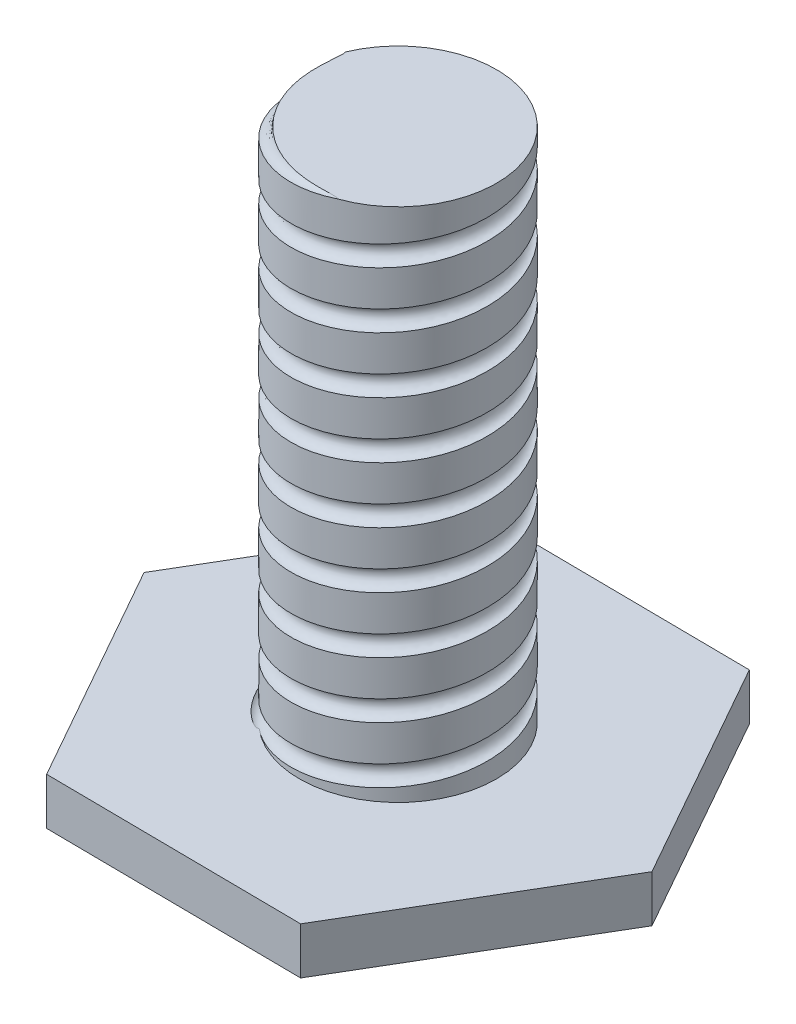
SolidWorks part; units mm, degrees
ref_plane "Front Plane" through (0, 0, 0) normal (0, 0, 1) x (1, 0, 0)
ref_plane "Top Plane" through (0, 0, 0) normal (0, 1, 0) x (1, 0, 0)
ref_plane "Right Plane" through (0, 0, 0) normal (1, 0, 0) x (0, 0, -1)
sketch "Sketch1" plane through (0, 0, 0) normal (0, 1, 0) x (1, 0, 0)
  line L1 (26.8762, -47.6442) -> (54.6992, -0.5466)
  line L2 (54.6992, -0.5466) -> (27.823, 47.0976)
  line L3 (27.823, 47.0976) -> (-26.8762, 47.6442)
  line L4 (-26.8762, 47.6442) -> (-54.6992, 0.5466)
  line L5 (-54.6992, 0.5466) -> (-27.823, -47.0976)
  line L6 (-27.823, -47.0976) -> (26.8762, -47.6442)
  circle A0 centre (0, 0) radius 47.3733 construction
extrude "Boss-Extrude1" add sketch "Sketch1" along normal blind 10
sketch "Sketch2" plane through (0, 10, 0) normal (0, 1, 0) x (1, 0, 0)
  circle A0 centre (0, 0) radius 21.0099
extrude "Boss-Extrude2" add sketch "Sketch2" along normal blind 110
sketch "Sketch4" plane through (0, 120, 0) normal (0, 1, 0) x (1, 0, 0)
  circle A0 centre (0, 0) radius 21.0099
curve "Helix/Spiral2" pitch 12 height 108 turns 9
sketch "Sketch5" plane through (0, 0, 0) normal (0, 0, 1) x (1, 0, 0)
  circle A0 centre (-21.0896, 118.553) radius 2.2003
sweep "Cut-Sweep1" cut profiles "Sketch5" path "Helix/Spiral2"
